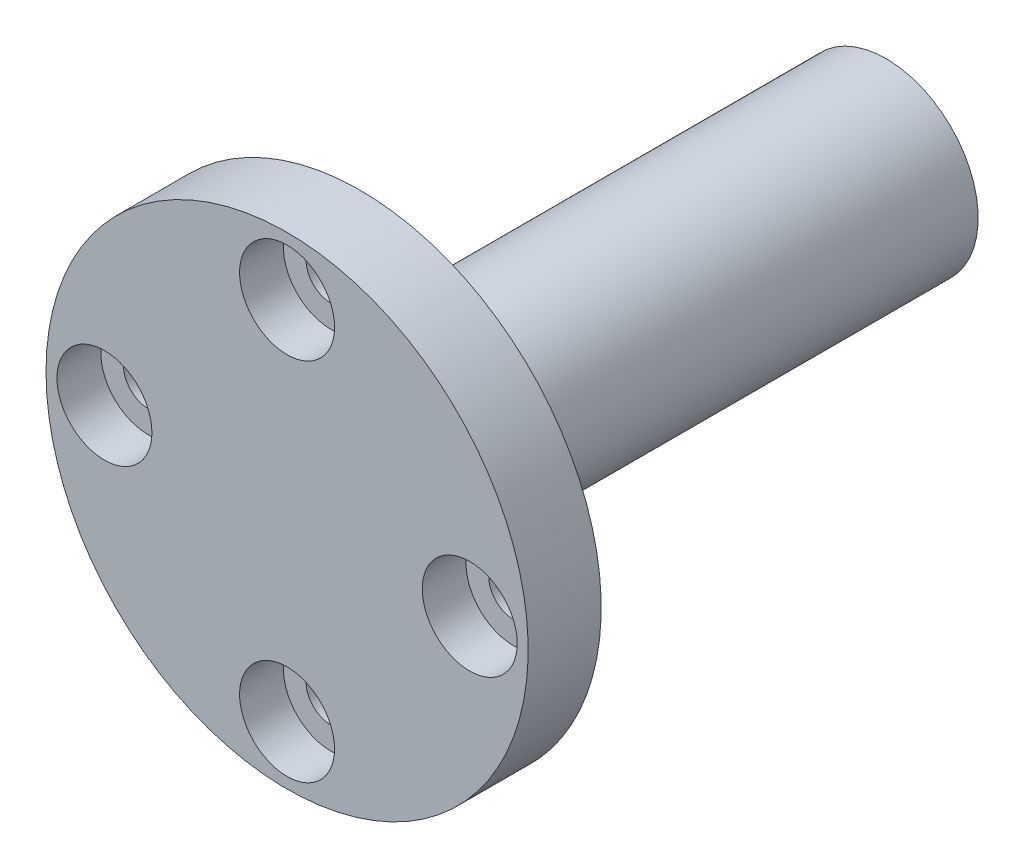
SolidWorks part; units mm, degrees
material "3.1355 (EN-AW 2024)"
ref_plane "Front" through (0, 0, 0) normal (0, 0, 1) x (1, 0, 0)
ref_plane "Top" through (0, 0, 0) normal (0, 1, 0) x (1, 0, 0)
ref_plane "Right" through (0, 0, 0) normal (1, 0, 0) x (0, 0, -1)
sketch "Эскиз2" plane through (0, 0, 0) normal (1, 0, 0) x (0, 0, -1)
  line L0 (0, 0) -> (0, 16.5)
  line L1 (0, 16.5) -> (5, 16.5)
  line L2 (5, 16.5) -> (5, 6.3)
  line L3 (5, 6.3) -> (41, 6.3)
  line L4 (41, 6.3) -> (41, 0)
  line L5 (41, 0) -> (0, 0)
  dimension "D1" = 16.5
  dimension "D2" = 5
  dimension "D3" = 6.3
  dimension "D4" = 36
  dimension "D5" = 41
revolve "Повернуть1" add sketch "Эскиз2" angle 360 about L5
sketch "Эскиз3" plane through (0, 0, 0) normal (0, 0, 1) x (1, 0, 0)
  circle A0 centre (0, 0) radius 12.5 construction
  point P3 (0, 12.5)
  point P7 (12.5, 0)
  point P8 (0, -12.5)
  point P9 (-12.5, 0)
  point P10 (0, 0)
  dimension "D1" = 25
  dimension "D2" = 4
hole_wizard "Цековка для винта с внутренним шестигранником M31" positions "Эскиз5" profile "Эскиз4" counterbore size "M3" standard "Ansi Metric" end condition through all
sketch "Эскиз5" plane through (0, 0, 0) normal (0, 0, 1) x (1, 0, 0)
  point P0 (-12.5, 0)
  point P3 (0, 12.5)
  point P6 (12.5, 0)
  point P9 (0, -12.5)
sketch "Эскиз4" plane through (-12.5, 0, 0) normal (1, 0, 0) x (0, -1, 0)
  line L0 (0, 0) -> (0, 41)
  line L1 (0, 41) -> (1.7, 41)
  line L3 (1.7, 41) -> (1.7, 3)
  line L4 (1.7, 3) -> (3.25, 3)
  line L5 (3.25, 3) -> (3.25, 0)
  line L7 (3.25, 0) -> (0, 0)
  line L11 (0, -6.35) -> (0, 107.95) construction
  dimension "Диаметр сквозного отверстия" = 3.4
  dimension "Глубина сквозного отверстия" = 41
  dimension "Диаметр цековки" = 6.5
  dimension "Глубина цековки" = 3
